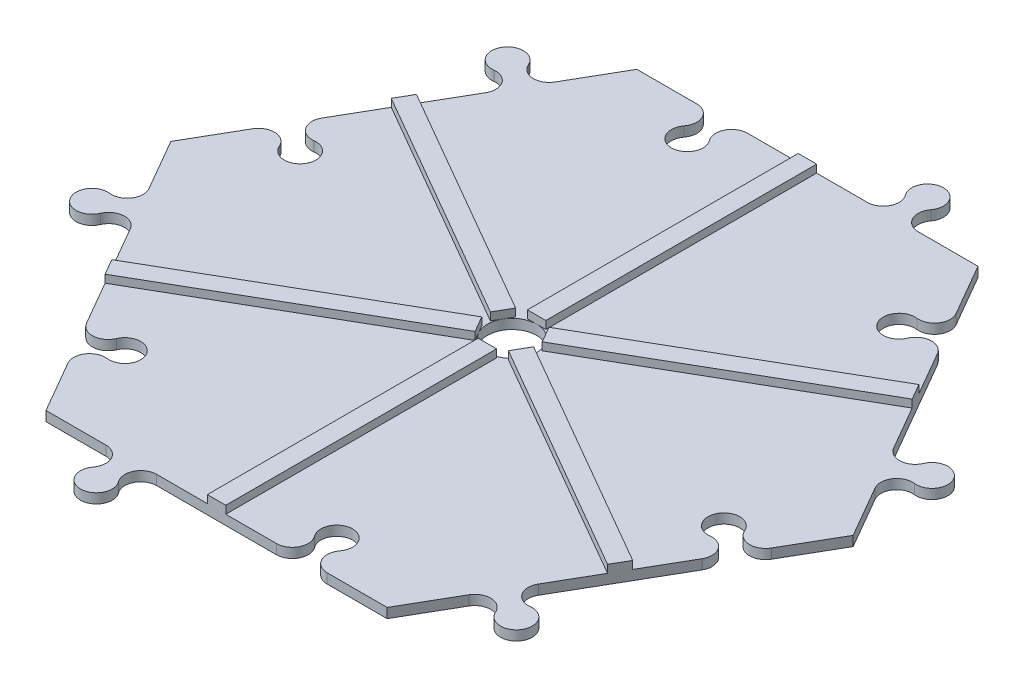
SolidWorks part; units mm, degrees
ref_plane "Front Plane" through (0, 0, 0) normal (0, 0, 1) x (1, 0, 0)
ref_plane "Top Plane" through (0, 0, 0) normal (0, 1, 0) x (1, 0, 0)
ref_plane "Right Plane" through (0, 0, 0) normal (1, 0, 0) x (0, 0, -1)
sketch "Sketch1" plane through (0, 0, 0) normal (0, 1, 0) x (1, 0, 0)
  line L10 (55.5, -96.1288) -> (111, 0)
  line L11 (111, 0) -> (55.5, 96.1288)
  line L12 (55.5, 96.1288) -> (-55.5, 96.1288)
  line L13 (-55.5, 96.1288) -> (-111, 0)
  line L14 (-111, 0) -> (-55.5, -96.1288)
  line L15 (-55.5, -96.1288) -> (55.5, -96.1288)
  circle A3 centre (0, 0) radius 96.1288 construction
  dimension "D1" = 111
extrude "Boss-Extrude1" add sketch "Sketch1" along normal blind 3.175 contours L14 L15 L10 L11 L12 L13
sketch "Sketch2" plane through (0, 0, 0) normal (0, 1, 0) x (1, 0, 0)
  line L0 (-19.495, 96.1288) -> (-36.005, 96.1288)
  line L1 (0, 0) -> (0, 96.1288) construction
  line L2 (0, 96.1288) -> (55.5, 96.1288) construction
  line L4 (27.75, 96.1288) -> (27.75, 118.9888) construction
  line L5 (19.495, 96.1288) -> (36.005, 96.1288)
  line L7 (55.5, 96.1288) -> (-55.5, 96.1288) construction
  arc A0 (-31.8775, 104.3838) -> (-27.75, 112.6388) centre (-27.75, 107.4794) cw construction
  arc A1 (-23.6225, 104.3838) -> (-27.75, 112.6388) centre (-27.75, 107.4794) ccw construction
  arc A2 (-19.495, 96.1288) -> (-23.6225, 104.3838) centre (-19.495, 101.2882) cw construction
  arc A3 (19.495, 96.1288) -> (23.6225, 104.3838) centre (19.495, 101.2882) ccw
  arc A4 (-36.005, 96.1288) -> (-31.8775, 104.3838) centre (-36.005, 101.2882) ccw construction
  arc A5 (23.6225, 104.3838) -> (27.75, 112.6388) centre (27.75, 107.4794) cw
  arc A7 (36.005, 96.1288) -> (31.8775, 104.3838) centre (36.005, 101.2882) cw
  arc A8 (31.8775, 104.3838) -> (27.75, 112.6388) centre (27.75, 107.4794) ccw
  arc A9 (-19.495, 96.1288) -> (-23.6225, 87.8738) centre (-19.495, 90.9694) ccw
  arc A10 (-23.6225, 87.8738) -> (-27.75, 79.6188) centre (-27.75, 84.7782) cw
  arc A11 (-31.8775, 87.8738) -> (-27.75, 79.6188) centre (-27.75, 84.7782) ccw
  arc A12 (-36.005, 96.1288) -> (-31.8775, 87.8738) centre (-36.005, 90.9694) cw
  dimension "D1" = 22.86
  dimension "D3" = 16.51
  dimension "D4" = 16.51
extrude "Boss-Extrude2" add sketch "Sketch2" along normal up to surface (3.175 mm away) contours A7 A8 A5 A3 L5 up to face at (0, 3.175, 0)
extrude "Cut-Extrude2" cut sketch "Sketch2<3>" along normal through all contours A11 A10 A9 L0 A12
sketch "Sketch2<3>" plane through (0, 0, 0) normal (0, 1, 0) x (1, 0, 0) same geometry as "Sketch2"
sketch "Sketch3" [suppressed] plane through (0, 0, 0) normal (0, 0, 1) x (1, 0, 0)
  line L0 (0, 0) -> (0, 25.4) construction
  dimension "D1" = 25.4
pattern_circular "CirPattern1" count 6 over 360 about axis through (0, 0, 0) along (0, 1, 0) of "Boss-Extrude2", "Cut-Extrude2" reverse direction yes
sketch "Sketch4" plane through (0, 3.175, 0) normal (0, 1, 0) x (1, 0, 0)
  circle A0 centre (0, 0) radius 8.001
  dimension "D1" = 16.002
extrude "Cut-Extrude3" cut sketch "Sketch4" against normal up to surface (3.175 mm away) up to face at (0, 0, 0)
sketch "Sketch5" plane through (0, 3.175, 0) normal (0, 1, 0) x (1, 0, 0)
  line L0 (-84.75, -45.4663) -> (-7.9236, -1.1106)
  line L1 (-81.75, -50.6625) -> (-4.9236, -6.3067)
  line L2 (-92.9975, -31.1812) -> (-73.5025, -64.9476) construction
  line L3 (-83.25, -48.0644) -> (-6.9291, -4.0005) construction
  line L4 (-7.9236, -1.1106) -> (-4.9236, -6.3067)
  line L5 (-92.9975, -31.1812) -> (-73.5025, -64.9476) construction
  line L6 (-84.75, -45.4663) -> (-81.75, -50.6625)
  line L7 (-5.4291, -6.5986) -> (-8.4291, -1.4024)
  circle A0 centre (0, 0) radius 8.001 construction
  arc A1 (-7.9236, -1.1106) -> (-4.9236, -6.3067) centre (0, 0) ccw
  dimension "D1" = 6
extrude "Boss-Extrude3" add sketch "Sketch5" along normal blind 2.54 contours L6 L3 L7 L0 | L3 L6 L1 L7 region at (-45.8395, 3.175, 24.7334) region at (-44.3395, 3.175, 27.3315)
pattern_circular "CirPattern2" count 6 over 360 about axis through (0, -22.6302, 0) along (0, 1, 0) of "Boss-Extrude3"
sketch "Sketch6" plane through (0, 3.175, 0) normal (0, 1, 0) x (1, 0, 0)
  line L0 (-81.75, 50.6625) -> (-5.4291, 6.5986) construction
  line L1 (-5.4291, 6.5986) -> (-6.9291, 4.0005) construction
  line L2 (0, 8.001) -> (-3, 8.001) construction
  line L3 (-3, 8.001) -> (-3, 96.1288) construction
  line L4 (-3, 96.1288) -> (-19.495, 96.1288) construction
  line L5 (-36.005, 96.1288) -> (-55.5, 96.1288) construction
  line L6 (-55.5, 96.1288) -> (-65.2475, 79.2457) construction
  line L7 (-73.5025, 64.9476) -> (-81.75, 50.6625) construction
  line L8 (-6.9291, 4.0005) -> (-8.4291, 1.4024) construction
  line L9 (-8.4291, 1.4024) -> (-84.75, 45.4663) construction
  line L10 (-84.75, 45.4663) -> (-92.9975, 31.1812) construction
  line L11 (-101.2525, 16.8832) -> (-111, 0) construction
  line L12 (-111, 0) -> (-101.2525, -16.8832) construction
  line L13 (-92.9975, -31.1812) -> (-84.75, -45.4663) construction
  line L14 (-84.75, -45.4663) -> (-8.4291, -1.4024) construction
  line L15 (-8.4291, -1.4024) -> (-6.9291, -4.0005) construction
  line L16 (-3, -96.1288) -> (-3, -8.001) construction
  line L17 (-3, -8.001) -> (0, -8.001) construction
  line L18 (-6.9291, -4.0005) -> (-5.4291, -6.5986) construction
  line L19 (-5.4291, -6.5986) -> (-81.75, -50.6625) construction
  line L20 (-81.75, -50.6625) -> (-73.5025, -64.9476) construction
  line L21 (-65.2475, -79.2457) -> (-55.5, -96.1288) construction
  line L22 (-55.5, -96.1288) -> (-36.005, -96.1288) construction
  line L23 (-19.495, -96.1288) -> (-3, -96.1288) construction
  line L24 (81.75, -50.6625) -> (5.4291, -6.5986) construction
  line L25 (5.4291, -6.5986) -> (6.9291, -4.0005) construction
  line L26 (0, -8.001) -> (3, -8.001) construction
  line L27 (3, -8.001) -> (3, -96.1288) construction
  line L28 (3, -96.1288) -> (19.495, -96.1288) construction
  line L29 (36.005, -96.1288) -> (55.5, -96.1288) construction
  line L30 (55.5, -96.1288) -> (65.2475, -79.2457) construction
  line L31 (73.5025, -64.9476) -> (81.75, -50.6625) construction
  line L32 (84.75, 45.4663) -> (8.4291, 1.4024) construction
  line L33 (8.4291, 1.4024) -> (6.9291, 4.0005) construction
  line L34 (6.9291, -4.0005) -> (8.4291, -1.4024) construction
  line L35 (8.4291, -1.4024) -> (84.75, -45.4663) construction
  line L36 (84.75, -45.4663) -> (92.9975, -31.1812) construction
  line L37 (101.2525, -16.8832) -> (111, 0) construction
  line L38 (111, 0) -> (101.2525, 16.8832) construction
  line L39 (92.9975, 31.1812) -> (84.75, 45.4663) construction
  line L40 (3, 96.1288) -> (3, 8.001) construction
  line L41 (3, 8.001) -> (0, 8.001) construction
  line L42 (6.9291, 4.0005) -> (5.4291, 6.5986) construction
  line L43 (5.4291, 6.5986) -> (81.75, 50.6625) construction
  line L44 (81.75, 50.6625) -> (73.5025, 64.9476) construction
  line L45 (65.2475, 79.2457) -> (55.5, 96.1288) construction
  line L46 (55.5, 96.1288) -> (36.005, 96.1288) construction
  line L47 (19.495, 96.1288) -> (3, 96.1288) construction
  line L48 (-81.75, 50.6625) -> (-5.4291, 6.5986)
  line L49 (-5.4291, 6.5986) -> (-6.9291, 4.0005)
  line L50 (0, 8.001) -> (-3, 8.001)
  line L51 (-3, 8.001) -> (-3, 96.1288)
  line L52 (-3, 96.1288) -> (-19.495, 96.1288)
  line L53 (-36.005, 96.1288) -> (-55.5, 96.1288)
  line L54 (-55.5, 96.1288) -> (-65.2475, 79.2457)
  line L55 (-73.5025, 64.9476) -> (-81.75, 50.6625)
  line L56 (-6.9291, 4.0005) -> (-8.4291, 1.4024)
  line L57 (-8.4291, 1.4024) -> (-84.75, 45.4663)
  line L58 (-84.75, 45.4663) -> (-92.9975, 31.1812)
  line L59 (-101.2525, 16.8832) -> (-111, 0)
  line L60 (-111, 0) -> (-101.2525, -16.8832)
  line L61 (-92.9975, -31.1812) -> (-84.75, -45.4663)
  line L62 (-84.75, -45.4663) -> (-8.4291, -1.4024)
  line L63 (-8.4291, -1.4024) -> (-6.9291, -4.0005)
  line L64 (-3, -96.1288) -> (-3, -8.001)
  line L65 (-3, -8.001) -> (0, -8.001)
  line L66 (-6.9291, -4.0005) -> (-5.4291, -6.5986)
  line L67 (-5.4291, -6.5986) -> (-81.75, -50.6625)
  line L68 (-81.75, -50.6625) -> (-73.5025, -64.9476)
  line L69 (-65.2475, -79.2457) -> (-55.5, -96.1288)
  line L70 (-55.5, -96.1288) -> (-36.005, -96.1288)
  line L71 (-19.495, -96.1288) -> (-3, -96.1288)
  line L72 (81.75, -50.6625) -> (5.4291, -6.5986)
  line L73 (5.4291, -6.5986) -> (6.9291, -4.0005)
  line L74 (0, -8.001) -> (3, -8.001)
  line L75 (3, -8.001) -> (3, -96.1288)
  line L76 (3, -96.1288) -> (19.495, -96.1288)
  line L77 (36.005, -96.1288) -> (55.5, -96.1288)
  line L78 (55.5, -96.1288) -> (65.2475, -79.2457)
  line L79 (73.5025, -64.9476) -> (81.75, -50.6625)
  line L80 (84.75, 45.4663) -> (8.4291, 1.4024)
  line L81 (8.4291, 1.4024) -> (6.9291, 4.0005)
  line L82 (6.9291, -4.0005) -> (8.4291, -1.4024)
  line L83 (8.4291, -1.4024) -> (84.75, -45.4663)
  line L84 (84.75, -45.4663) -> (92.9975, -31.1812)
  line L85 (101.2525, -16.8832) -> (111, 0)
  line L86 (111, 0) -> (101.2525, 16.8832)
  line L87 (92.9975, 31.1812) -> (84.75, 45.4663)
  line L88 (3, 96.1288) -> (3, 8.001)
  line L89 (3, 8.001) -> (0, 8.001)
  line L90 (6.9291, 4.0005) -> (5.4291, 6.5986)
  line L91 (5.4291, 6.5986) -> (81.75, 50.6625)
  line L92 (81.75, 50.6625) -> (73.5025, 64.9476)
  line L93 (65.2475, 79.2457) -> (55.5, 96.1288)
  line L94 (55.5, 96.1288) -> (36.005, 96.1288)
  line L95 (19.495, 96.1288) -> (3, 96.1288)
  arc A1 (-19.495, 96.1288) -> (-23.6225, 87.8738) centre (-19.495, 90.9694) ccw construction
  arc A2 (-31.8775, 87.8738) -> (-23.6225, 87.8738) centre (-27.75, 84.7782) ccw construction
  arc A3 (-31.8775, 87.8738) -> (-36.005, 96.1288) centre (-36.005, 90.9694) ccw construction
  arc A4 (-74.4603, 79.7986) -> (-65.2475, 79.2457) centre (-69.7156, 81.8253) ccw construction
  arc A5 (-74.4603, 79.7986) -> (-78.5878, 72.6496) centre (-79.2049, 77.7719) ccw construction
  arc A6 (-73.5025, 64.9476) -> (-78.5878, 72.6496) centre (-77.9706, 67.5273) ccw construction
  arc A7 (-92.9975, 31.1812) -> (-87.9122, 23.4792) centre (-88.5294, 28.6016) ccw construction
  arc A8 (-92.0397, 16.3302) -> (-87.9122, 23.4792) centre (-87.2951, 18.3569) ccw construction
  arc A9 (-92.0397, 16.3302) -> (-101.2525, 16.8832) centre (-96.7844, 14.3035) ccw construction
  arc A10 (-106.3378, -24.5852) -> (-101.2525, -16.8832) centre (-105.7206, -19.4629) ccw construction
  arc A11 (-106.3378, -24.5852) -> (-102.2103, -31.7342) centre (-106.9549, -29.7075) ccw construction
  arc A12 (-92.9975, -31.1812) -> (-102.2103, -31.7342) centre (-97.4656, -33.7609) ccw construction
  arc A15 (-73.5025, -64.9476) -> (-64.2897, -64.3946) centre (-69.0344, -62.3679) ccw construction
  arc A16 (-60.1622, -71.5436) -> (-64.2897, -64.3946) centre (-59.5451, -66.4213) ccw construction
  arc A17 (-60.1622, -71.5436) -> (-65.2475, -79.2457) centre (-60.7794, -76.666) ccw construction
  arc A18 (-31.8775, -104.3838) -> (-36.005, -96.1288) centre (-36.005, -101.2882) ccw construction
  arc A19 (-31.8775, -104.3838) -> (-23.6225, -104.3838) centre (-27.75, -107.4794) ccw construction
  arc A20 (-19.495, -96.1288) -> (-23.6225, -104.3838) centre (-19.495, -101.2882) ccw construction
  arc A22 (19.495, -96.1288) -> (23.6225, -87.8738) centre (19.495, -90.9694) ccw construction
  arc A23 (31.8775, -87.8738) -> (23.6225, -87.8738) centre (27.75, -84.7782) ccw construction
  arc A24 (31.8775, -87.8738) -> (36.005, -96.1288) centre (36.005, -90.9694) ccw construction
  arc A25 (74.4603, -79.7986) -> (65.2475, -79.2457) centre (69.7156, -81.8253) ccw construction
  arc A26 (74.4603, -79.7986) -> (78.5878, -72.6496) centre (79.2049, -77.7719) ccw construction
  arc A27 (73.5025, -64.9476) -> (78.5878, -72.6496) centre (77.9706, -67.5273) ccw construction
  arc A29 (92.9975, -31.1812) -> (87.9122, -23.4792) centre (88.5294, -28.6016) ccw construction
  arc A30 (92.0397, -16.3302) -> (87.9122, -23.4792) centre (87.2951, -18.3569) ccw construction
  arc A31 (92.0397, -16.3302) -> (101.2525, -16.8832) centre (96.7844, -14.3035) ccw construction
  arc A32 (106.3378, 24.5852) -> (101.2525, 16.8832) centre (105.7206, 19.4629) ccw construction
  arc A33 (106.3378, 24.5852) -> (102.2103, 31.7342) centre (106.9549, 29.7075) ccw construction
  arc A34 (92.9975, 31.1812) -> (102.2103, 31.7342) centre (97.4656, 33.7609) ccw construction
  arc A36 (73.5025, 64.9476) -> (64.2897, 64.3946) centre (69.0344, 62.3679) ccw construction
  arc A37 (60.1622, 71.5436) -> (64.2897, 64.3946) centre (59.5451, 66.4213) ccw construction
  arc A38 (60.1622, 71.5436) -> (65.2475, 79.2457) centre (60.7794, 76.666) ccw construction
  arc A39 (31.8775, 104.3838) -> (36.005, 96.1288) centre (36.005, 101.2882) ccw construction
  arc A40 (31.8775, 104.3838) -> (23.6225, 104.3838) centre (27.75, 107.4794) ccw construction
  arc A41 (19.495, 96.1288) -> (23.6225, 104.3838) centre (19.495, 101.2882) ccw construction
  arc A43 (-19.495, 96.1288) -> (-23.6225, 87.8738) centre (-19.495, 90.9694) ccw
  arc A44 (-31.8775, 87.8738) -> (-23.6225, 87.8738) centre (-27.75, 84.7782) ccw
  arc A45 (-31.8775, 87.8738) -> (-36.005, 96.1288) centre (-36.005, 90.9694) ccw
  arc A46 (-74.4603, 79.7986) -> (-65.2475, 79.2457) centre (-69.7156, 81.8253) ccw
  arc A47 (-74.4603, 79.7986) -> (-78.5878, 72.6496) centre (-79.2049, 77.7719) ccw
  arc A48 (-73.5025, 64.9476) -> (-78.5878, 72.6496) centre (-77.9706, 67.5273) ccw
  arc A49 (-92.9975, 31.1812) -> (-87.9122, 23.4792) centre (-88.5294, 28.6016) ccw
  arc A50 (-92.0397, 16.3302) -> (-87.9122, 23.4792) centre (-87.2951, 18.3569) ccw
  arc A51 (-92.0397, 16.3302) -> (-101.2525, 16.8832) centre (-96.7844, 14.3035) ccw
  arc A52 (-106.3378, -24.5852) -> (-101.2525, -16.8832) centre (-105.7206, -19.4629) ccw
  arc A53 (-106.3378, -24.5852) -> (-102.2103, -31.7342) centre (-106.9549, -29.7075) ccw
  arc A54 (-92.9975, -31.1812) -> (-102.2103, -31.7342) centre (-97.4656, -33.7609) ccw
  arc A57 (-73.5025, -64.9476) -> (-64.2897, -64.3946) centre (-69.0344, -62.3679) ccw
  arc A58 (-60.1622, -71.5436) -> (-64.2897, -64.3946) centre (-59.5451, -66.4213) ccw
  arc A59 (-60.1622, -71.5436) -> (-65.2475, -79.2457) centre (-60.7794, -76.666) ccw
  arc A60 (-31.8775, -104.3838) -> (-36.005, -96.1288) centre (-36.005, -101.2882) ccw
  arc A61 (-31.8775, -104.3838) -> (-23.6225, -104.3838) centre (-27.75, -107.4794) ccw
  arc A62 (-19.495, -96.1288) -> (-23.6225, -104.3838) centre (-19.495, -101.2882) ccw
  arc A64 (19.495, -96.1288) -> (23.6225, -87.8738) centre (19.495, -90.9694) ccw
  arc A65 (31.8775, -87.8738) -> (23.6225, -87.8738) centre (27.75, -84.7782) ccw
  arc A66 (31.8775, -87.8738) -> (36.005, -96.1288) centre (36.005, -90.9694) ccw
  arc A67 (74.4603, -79.7986) -> (65.2475, -79.2457) centre (69.7156, -81.8253) ccw
  arc A68 (74.4603, -79.7986) -> (78.5878, -72.6496) centre (79.2049, -77.7719) ccw
  arc A69 (73.5025, -64.9476) -> (78.5878, -72.6496) centre (77.9706, -67.5273) ccw
  arc A71 (92.9975, -31.1812) -> (87.9122, -23.4792) centre (88.5294, -28.6016) ccw
  arc A72 (92.0397, -16.3302) -> (87.9122, -23.4792) centre (87.2951, -18.3569) ccw
  arc A73 (92.0397, -16.3302) -> (101.2525, -16.8832) centre (96.7844, -14.3035) ccw
  arc A74 (106.3378, 24.5852) -> (101.2525, 16.8832) centre (105.7206, 19.4629) ccw
  arc A75 (106.3378, 24.5852) -> (102.2103, 31.7342) centre (106.9549, 29.7075) ccw
  arc A76 (92.9975, 31.1812) -> (102.2103, 31.7342) centre (97.4656, 33.7609) ccw
  arc A78 (73.5025, 64.9476) -> (64.2897, 64.3946) centre (69.0344, 62.3679) ccw
  arc A79 (60.1622, 71.5436) -> (64.2897, 64.3946) centre (59.5451, 66.4213) ccw
  arc A80 (60.1622, 71.5436) -> (65.2475, 79.2457) centre (60.7794, 76.666) ccw
  arc A81 (31.8775, 104.3838) -> (36.005, 96.1288) centre (36.005, 101.2882) ccw
  arc A82 (31.8775, 104.3838) -> (23.6225, 104.3838) centre (27.75, 107.4794) ccw
  arc A83 (19.495, 96.1288) -> (23.6225, 104.3838) centre (19.495, 101.2882) ccw
sketch "Sketch7" plane through (0, 5.715, 0) normal (0, 1, 0) x (1, 0, 0)
  line L4 (3, 96.1288) -> (-3, 96.1288)
  line L5 (-3, 96.1288) -> (-3, 8.001)
  line L6 (-3, 8.001) -> (3, 8.001)
  line L7 (3, 8.001) -> (3, 96.1288)
  line L8 (3, 96.1288) -> (-3, 96.1288)
  line L9 (-3, 96.1288) -> (-3, 8.001)
  line L10 (-3, 8.001) -> (3, 8.001)
  line L11 (3, 8.001) -> (3, 96.1288)
  dimension "D1" = 0
